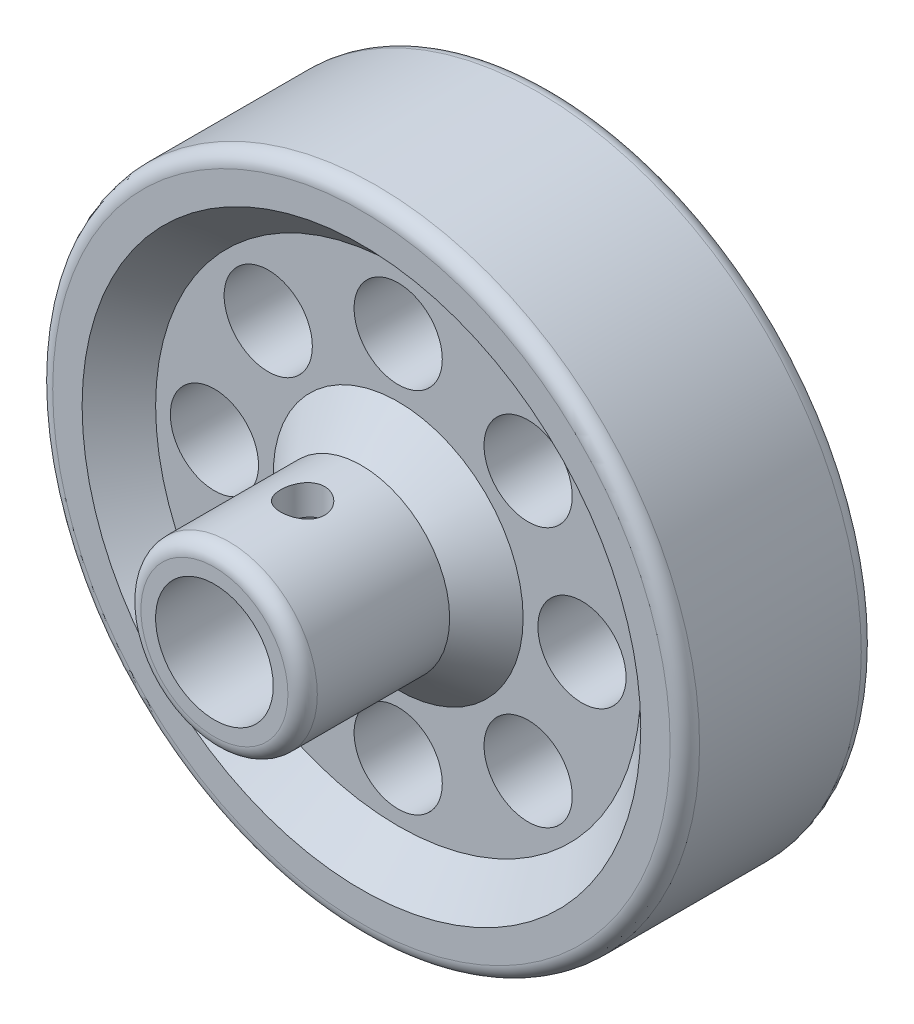
SolidWorks part; units mm, degrees
material "Chrome Stainless Steel"
ref_plane "Front Plane" through (0, 0, 0) normal (0, 0, 1) x (1, 0, 0)
ref_plane "Top Plane" through (0, 0, 0) normal (0, 1, 0) x (1, 0, 0)
ref_plane "Right Plane" through (0, 0, 0) normal (1, 0, 0) x (0, 0, -1)
sketch "Sketch1" plane through (0, 0, 0) normal (0, 0, 1) x (1, 0, 0)
  circle A0 centre (0, 0) radius 22
  circle A1 centre (0, 0) radius 19
  dimension "D1" = 38
  dimension "D2" = 44
extrude "Boss-Extrude1" add sketch "Sketch1" along normal mid plane 13
sketch "Sketch2" plane through (0, 0, 0) normal (0, 0, 1) x (1, 0, 0)
  circle A0 centre (0, 0) radius 19
extrude "Boss-Extrude2" add sketch "Sketch2" along normal mid plane 8
chamfer "Chamfer1" distance 2.5 angle 45 2 edges at (19, 0, 4) (19, 0, -4)
sketch "Sketch3" plane through (0, 0, 0) normal (0, 0, 1) x (1, 0, 0)
  line L0 (15.7611, 0) -> (-14.7103, 0) construction
  line L1 (0, -11.4455) -> (0, 14.973) construction
  line L2 (0, 0) -> (19.9504, -19.9504) construction
  circle A0 centre (0, 0) radius 12.5 construction
  circle A1 centre (0, 0) radius 8.5 construction
  circle A2 centre (0, 12.5) radius 3
  circle A13 centre (8.8388, 8.8388) radius 3
  circle A14 centre (12.5, 0) radius 3
  circle A15 centre (8.8388, -8.8388) radius 3
  circle A16 centre (0, -12.5) radius 3
  circle A17 centre (-8.8388, -8.8388) radius 3
  circle A18 centre (-12.5, 0) radius 3
  circle A19 centre (-8.8388, 8.8388) radius 3
  point P20 (0, 0)
  point P30 (0, 0)
  point P35 (0, 0)
  dimension "D1" = 25
  dimension "D2" = 8
extrude "Cut-Extrude1" cut sketch "Sketch3" against normal mid plane 8
sketch "Sketch5" plane through (0, 0, 0) normal (0, 0, 1) x (1, 0, 0)
  circle A0 centre (0, 0) radius 8.5
extrude "Boss-Extrude3" add sketch "Sketch5" along normal mid plane 13
chamfer "Chamfer3" distance 2.5 angle 45 2 edges at (8.5, 0, -6.5) (8.5, 0, 6.5)
sketch "Sketch6" plane through (0, 0, 6.5) normal (0, 0, 1) x (1, 0, 0)
  circle A0 centre (0, 0) radius 6
extrude "Boss-Extrude4" add sketch "Sketch6" along normal blind 10
fillet "Fillet2" radius 1 1 edges at (6, 0, 16.5)
sketch "Sketch7" plane through (0, 0, 16.5) normal (0, 0, 1) x (1, 0, 0)
  circle A0 centre (0, 0) radius 4
extrude "Cut-Extrude2" cut sketch "Sketch7" against normal blind 23
sketch "Sketch8" plane through (0, 0, 0) normal (0, 1, 0) x (1, 0, 0)
  line L0 (4, 6.5) -> (-4, 6.5) construction
  line L1 (6, -15.5) -> (6, -6.5) construction
  circle A0 centre (0, -10.5) radius 1.5
  dimension "D1" = 17
  dimension "D3" = 3
  dimension "D2" = 6
extrude "Cut-Extrude3" cut sketch "Sketch8" against normal mid plane 13
fillet "Fillet3" radius 1 2 edges at (22, 0, 6.5) (22, 0, -6.5)
